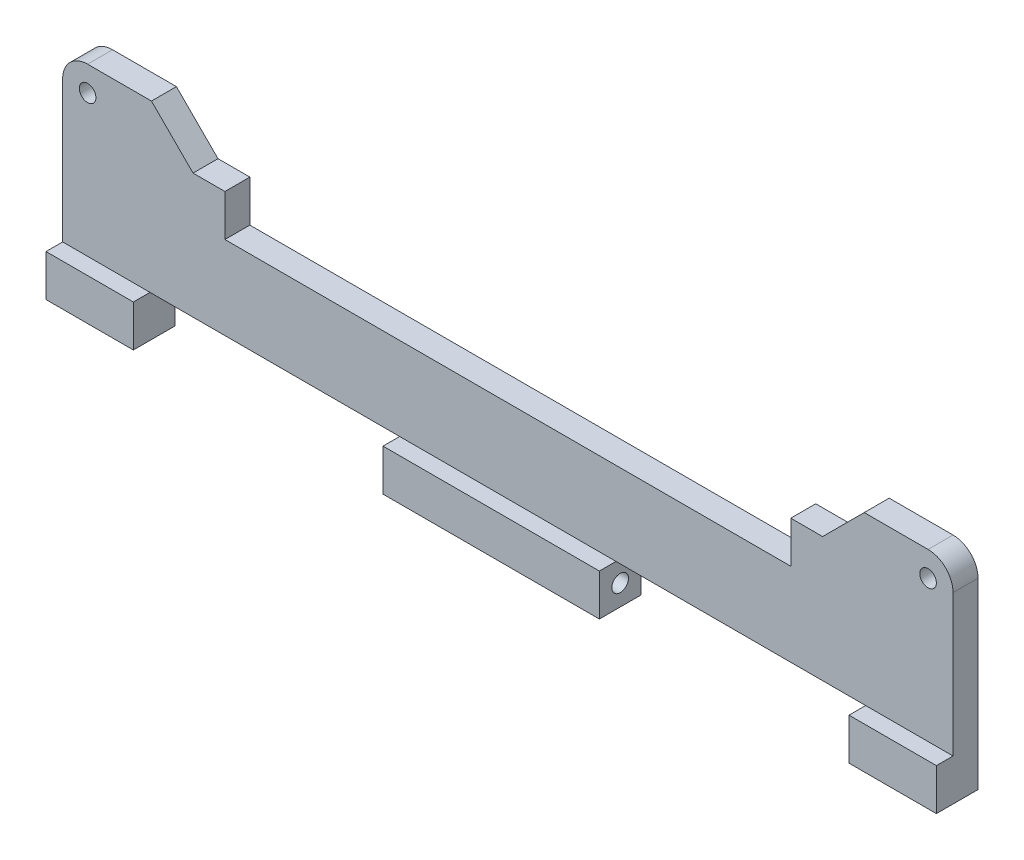
SolidWorks part; units mm, degrees
ref_plane "Plano frontal" through (0, 0, 0) normal (0, 0, 1) x (1, 0, 0)
ref_plane "Plano superior" through (0, 0, 0) normal (0, 1, 0) x (1, 0, 0)
ref_plane "Plano direito" through (0, 0, 0) normal (1, 0, 0) x (0, 0, -1)
sketch "Esboço1" plane through (0, 0, 0) normal (0, 0, 1) x (1, 0, 0)
  line L0 (-6, -5) -> (37, -5)
  line L1 (-16.5, -10) -> (-6, -10)
  line L2 (-16.5, -10) -> (-16.5, 10)
  line L4 (-16.5, 10) -> (37, 10)
  line L8 (-6, -10) -> (-6, -5)
  line L14 (37, 10) -> (37, -5)
  point P0 (0, 0)
  dimension "D1" = 53.5
extrude "Ressalto-extrusão1" add sketch "Esboço1" along normal blind 5
sketch "Esboço3" plane through (0, 0, 5) normal (0, 0, 1) x (1, 0, 0)
  line L2 (-16.5, -5) -> (103.0103, -5)
  line L3 (-16.5, -5) -> (-16.5, 10)
  line L4 (-16.5, 10) -> (103.0103, 10)
  line L5 (103.0103, -5) -> (103.0103, 10)
  line M3 (-16.5, 10) -> (-16.5, -10)
  dimension "D1" = 15
extrude "Corte-extrusão2" cut sketch "Esboço3" against normal blind 2 contours M3 region at (43.2552, 2.5, 5)
ref_plane "Plane1" through (-26.5, 0, 0) normal (-1, 0, 0) x (0, 0, 1)
ref_plane "Plano1" through (37, 0, 0) normal (1, 0, 0) x (0, 0, -1)
sketch "Esboço5" plane through (0, -5, 0) normal (0, -1, 0) x (1, 0, 0)
  line L0 (37, -1.65) -> (37, 1.65) construction
  line L1 (24, 0) -> (50, 0)
  line L2 (24, 0) -> (24, 5)
  line L3 (24, 5) -> (50, 5)
  line L4 (50, 0) -> (50, 5)
  line L5 (24, 0) -> (50, 5) construction
  line L6 (24, 5) -> (50, 0) construction
  point P0 (37, 2.5)
  dimension "D1" = 5
  dimension "D2" = 26
extrude "Ressalto-extrusão2" add sketch "Esboço5" along normal blind 5
sketch "Esboço6" plane through (50, 0, 0) normal (1, 0, 0) x (0, 0, -1)
  circle A0 centre (-2.5, -7.5) radius 1
extrude "Corte-extrusão4" cut sketch "Esboço6" against normal up to next
sketch "Esboço7" plane through (0, 10, 0) normal (0, 1, 0) x (1, 0, 0)
  line L0 (37, -3) -> (-16.5, -3) construction
  line L1 (-16.5, 0) -> (-10.8269, 0)
  line L2 (-16.5, 0) -> (-16.5, -3)
  line L3 (-16.5, -3) -> (-10.8269, -3)
  line L4 (-10.8269, 0) -> (-10.8269, -3)
extrude "Ressalto-extrusão4" add sketch "Esboço7" along normal blind 5
chamfer "Chanfro2" distance 10 angle 45 1 edges
fillet "Filete1" radius 3 1 edges at (-16.5, 15, 1.5)
sketch "Esboço8" plane through (0, 0, 0) normal (0, 0, -1) x (-1, 0, 0)
  line L0 (13.5, 15) -> (13.5, 12) construction
  line L1 (13.5, 12) -> (16.5, 12) construction
  circle A0 centre (13.5, 12) radius 1
extrude "Corte-extrusão6" cut sketch "Esboço8" against normal blind 5 contours A0
mirror "Espelhar2" about plane through (37, 0, 0) normal (1, 0, 0) of "Corte-extrusão2", "Ressalto-extrusão1", "Chanfro2", "Ressalto-extrusão4", "Filete1", "Corte-extrusão6"
sketch "Esboço10" plane through (0, 10, 0) normal (0, 1, 0) x (1, 0, 0)
  line L0 (37, -3) -> (37, 0) construction
  line L1 (74.8269, -3) -> (-0.8269, -3) construction
  line L2 (74.8269, 0) -> (-0.8269, 0) construction
  line L4 (3, -3) -> (71, -3)
  line L5 (3, -3) -> (3, 0)
  line L6 (3, 0) -> (71, 0)
  line L7 (71, -3) -> (71, 0)
  line L8 (3, -3) -> (71, 0) construction
  line L9 (3, 0) -> (71, -3) construction
  point P6 (37, -1.5)
  dimension "D1" = 68
extrude "Corte-extrusão7" cut sketch "Esboço10" against normal blind 5
